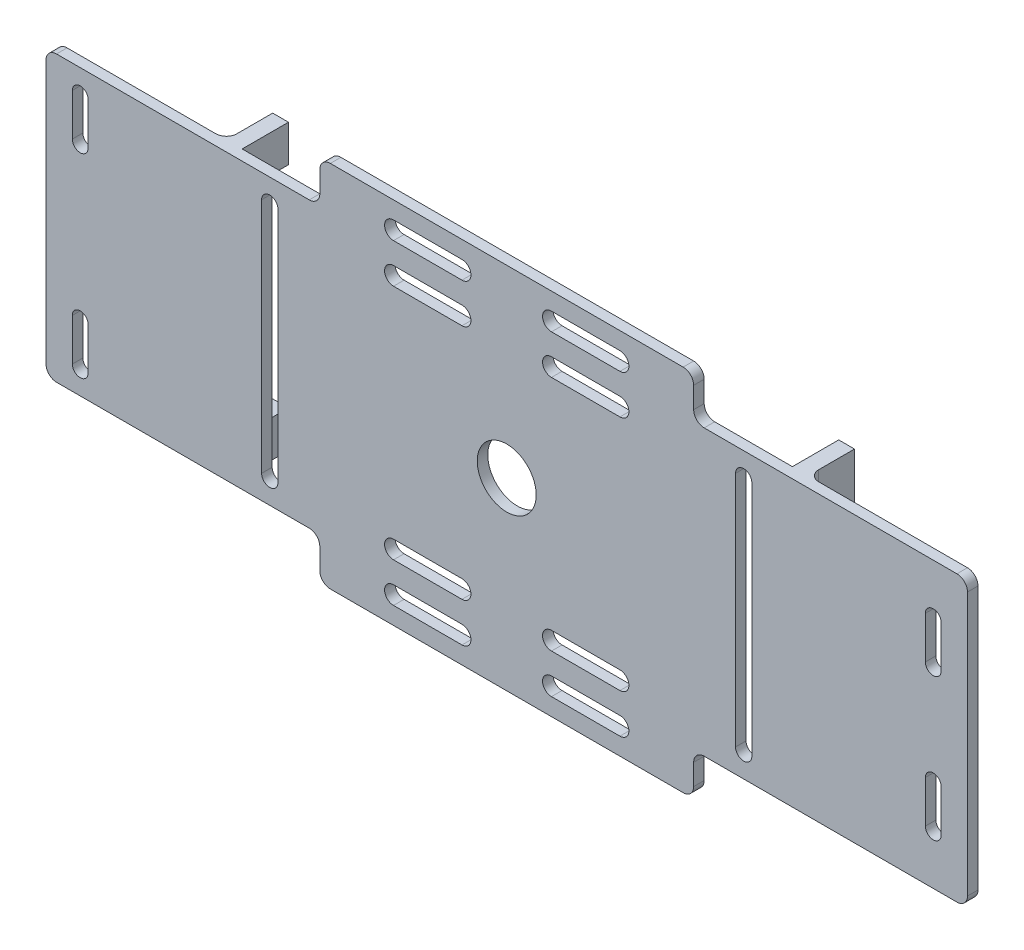
SolidWorks part; units mm, degrees
ref_plane "前基準面" through (0, 0, 0) normal (0, 0, 1) x (1, 0, 0)
ref_plane "上基準面" through (0, 0, 0) normal (0, 1, 0) x (1, 0, 0)
ref_plane "右基準面" through (0, 0, 0) normal (1, 0, 0) x (0, 0, -1)
sketch "草圖1" plane through (0, 0, 0) normal (0, 0, 1) x (1, 0, 0)
  line L0 (35.5, 33) -> (35.5, 29)
  line L1 (-33.5, 35) -> (33.5, 35)
  line L2 (-87.5, 25) -> (-87.5, -25)
  line L3 (-33.5, -35) -> (33.5, -35)
  line L4 (87.5, 25) -> (87.5, -25)
  line L5 (-85, 35) -> (85, -35) construction
  line L6 (-85, -35) -> (85, 35) construction
  line L7 (37.5, 27) -> (85.5, 27)
  line L8 (0, 72.342) -> (0, -45.5052) construction
  line L9 (-37.5, 27) -> (-85.5, 27)
  line L10 (124.9211, 0) -> (-91.026, 0) construction
  line L11 (-35.5, 33) -> (-35.5, 29)
  line L12 (37.5, -27) -> (85.5, -27)
  line L13 (35.5, -33) -> (35.5, -29)
  line L14 (-35.5, -33) -> (-35.5, -29)
  line L15 (-37.5, -27) -> (-85.5, -27)
  arc A0 (35.5, 33) -> (33.5, 35) centre (33.5, 33) ccw
  arc A1 (37.5, 27) -> (35.5, 29) centre (37.5, 29) cw
  arc A2 (87.5, 25) -> (85.5, 27) centre (85.5, 25) ccw
  arc A3 (-87.5, 25) -> (-85.5, 27) centre (-85.5, 25) cw
  arc A4 (-37.5, 27) -> (-35.5, 29) centre (-37.5, 29) ccw
  arc A5 (-35.5, 33) -> (-33.5, 35) centre (-33.5, 33) cw
  arc A6 (87.5, -25) -> (85.5, -27) centre (85.5, -25) cw
  arc A7 (37.5, -27) -> (35.5, -29) centre (37.5, -29) ccw
  arc A8 (35.5, -33) -> (33.5, -35) centre (33.5, -33) cw
  arc A9 (-35.5, -33) -> (-33.5, -35) centre (-33.5, -33) ccw
  arc A10 (-37.5, -27) -> (-35.5, -29) centre (-37.5, -29) cw
  arc A11 (-87.5, -25) -> (-85.5, -27) centre (-85.5, -25) ccw
  point P0 (0, 0)
  point P13 (35.5, 27)
  point P29 (-35.5, 27)
  point P39 (35.5, -27)
  point P49 (-35.5, -27)
  dimension "D1" = 2
  dimension "D2" = 2
  dimension "D3" = 2
  dimension "D4" = 175
  dimension "D5" = 70
  dimension "D6" = 52
  dimension "D7" = 8
extrude "填料-伸長1" add sketch "草圖1" along normal blind 2
sketch "草圖2" plane through (0, 0, 2) normal (0, 0, 1) x (1, 0, 0)
  line L0 (-1000, 0) -> (49000, 0) construction
  line L1 (45, -986.1952) -> (45, 49013.8048) construction
  line L2 (-81, -962.7943) -> (-81, 49037.2057) construction
  line L3 (45, -22.5) -> (45, 22.5) construction
  line L4 (43.45, -22.5) -> (43.45, 22.5)
  line L5 (46.55, -22.5) -> (46.55, 22.5)
  line L6 (-45, -1000) -> (-45, 49000) construction
  line L7 (-45, -22.5) -> (-45, 22.5) construction
  line L8 (-46.55, -22.5) -> (-46.55, 22.5)
  line L9 (-43.45, -22.5) -> (-43.45, 22.5)
  line L10 (0, -1000) -> (0, 49000) construction
  line L11 (-1005.6924, 30) -> (48994.3076, 30) construction
  line L12 (-1002.3566, -30) -> (48997.6434, -30) construction
  line L13 (21.5, 30) -> (8.5, 30) construction
  line L16 (21.5, 28.3) -> (8.5, 28.3)
  line L19 (81, -968.4295) -> (81, 49031.5705) construction
  line L20 (-81, -22.5) -> (-81, 22.5) construction
  line L21 (-82.5, -22.5) -> (-82.5, 22.5) construction
  line L22 (-79.5, -22.5) -> (-79.5, 22.5) construction
  line L23 (81, -17.5) -> (81, 17.5) construction
  line L24 (79.5, -17.5) -> (79.5, 17.5) construction
  line L25 (82.5, -17.5) -> (82.5, 17.5) construction
  line L26 (21.5, 31.7) -> (8.5, 31.7)
  line L27 (21.5, 22.5) -> (8.5, 22.5) construction
  line L28 (21.5, 20.8) -> (8.5, 20.8)
  line L29 (21.5, 24.2) -> (8.5, 24.2)
  line L30 (-21.5, 30) -> (-8.5, 30) construction
  line L31 (-21.5, 28.3) -> (-8.5, 28.3)
  line L32 (-21.5, 31.7) -> (-8.5, 31.7)
  line L33 (-21.5, 22.5) -> (-8.5, 22.5) construction
  line L34 (-21.5, 20.8) -> (-8.5, 20.8)
  line L35 (-21.5, 24.2) -> (-8.5, 24.2)
  line L36 (21.5, -30) -> (8.5, -30) construction
  line L37 (21.5, -28.3) -> (8.5, -28.3)
  line L38 (21.5, -31.7) -> (8.5, -31.7)
  line L39 (21.5, -22.5) -> (8.5, -22.5) construction
  line L40 (21.5, -20.8) -> (8.5, -20.8)
  line L41 (21.5, -24.2) -> (8.5, -24.2)
  line L42 (-21.5, -30) -> (-8.5, -30) construction
  line L43 (-21.5, -28.3) -> (-8.5, -28.3)
  line L44 (-21.5, -31.7) -> (-8.5, -31.7)
  line L45 (-21.5, -22.5) -> (-8.5, -22.5) construction
  line L46 (-21.5, -20.8) -> (-8.5, -20.8)
  line L47 (-21.5, -24.2) -> (-8.5, -24.2)
  line L48 (79.5, 9.5) -> (79.5, 17.5)
  line L49 (82.5, 17.5) -> (82.5, 9.5)
  line L50 (82.5, -17.5) -> (82.5, -9.5)
  line L51 (79.5, -9.5) -> (79.5, -17.5)
  line L52 (-82.5, 22.5) -> (-82.5, 14.5)
  line L53 (-79.5, 22.5) -> (-79.5, 14.5)
  line L54 (-79.5, -22.5) -> (-79.5, -14.5)
  line L55 (-82.5, -22.5) -> (-82.5, -14.5)
  arc A0 (43.45, -22.5) -> (46.55, -22.5) centre (45, -22.5) ccw
  arc A1 (46.55, 22.5) -> (43.45, 22.5) centre (45, 22.5) ccw
  arc A2 (-46.55, -22.5) -> (-43.45, -22.5) centre (-45, -22.5) ccw
  arc A3 (-43.45, 22.5) -> (-46.55, 22.5) centre (-45, 22.5) ccw
  arc A12 (-82.5, -22.5) -> (-79.5, -22.5) centre (-81, -22.5) ccw construction
  arc A13 (-79.5, 22.5) -> (-82.5, 22.5) centre (-81, 22.5) ccw construction
  arc A14 (79.5, -17.5) -> (82.5, -17.5) centre (81, -17.5) ccw construction
  arc A15 (82.5, 17.5) -> (79.5, 17.5) centre (81, 17.5) ccw construction
  circle A16 centre (0, 0) radius 5.6
  arc A17 (21.5, 28.3) -> (21.5, 31.7) centre (21.5, 30) ccw
  arc A18 (8.5, 31.7) -> (8.5, 28.3) centre (8.5, 30) ccw
  arc A19 (21.5, 20.8) -> (21.5, 24.2) centre (21.5, 22.5) ccw
  arc A20 (8.5, 24.2) -> (8.5, 20.8) centre (8.5, 22.5) ccw
  arc A21 (-21.5, 28.3) -> (-21.5, 31.7) centre (-21.5, 30) cw
  arc A22 (-8.5, 31.7) -> (-8.5, 28.3) centre (-8.5, 30) cw
  arc A23 (-21.5, 20.8) -> (-21.5, 24.2) centre (-21.5, 22.5) cw
  arc A24 (-8.5, 24.2) -> (-8.5, 20.8) centre (-8.5, 22.5) cw
  arc A25 (21.5, -28.3) -> (21.5, -31.7) centre (21.5, -30) cw
  arc A26 (8.5, -31.7) -> (8.5, -28.3) centre (8.5, -30) cw
  arc A27 (21.5, -20.8) -> (21.5, -24.2) centre (21.5, -22.5) cw
  arc A28 (8.5, -24.2) -> (8.5, -20.8) centre (8.5, -22.5) cw
  arc A29 (-21.5, -28.3) -> (-21.5, -31.7) centre (-21.5, -30) ccw
  arc A30 (-8.5, -31.7) -> (-8.5, -28.3) centre (-8.5, -30) ccw
  arc A31 (-21.5, -20.8) -> (-21.5, -24.2) centre (-21.5, -22.5) ccw
  arc A32 (-8.5, -24.2) -> (-8.5, -20.8) centre (-8.5, -22.5) ccw
  arc A33 (82.5, 9.5) -> (79.5, 9.5) centre (81, 9.5) cw
  arc A34 (82.5, -9.5) -> (79.5, -9.5) centre (81, -9.5) ccw
  arc A35 (79.5, 17.5) -> (82.5, 17.5) centre (81, 17.5) cw
  arc A36 (79.5, -17.5) -> (82.5, -17.5) centre (81, -17.5) ccw
  arc A37 (-82.5, -22.5) -> (-79.5, -22.5) centre (-81, -22.5) ccw
  arc A38 (-82.5, 22.5) -> (-79.5, 22.5) centre (-81, 22.5) cw
  arc A39 (-82.5, 14.5) -> (-79.5, 14.5) centre (-81, 14.5) ccw
  arc A40 (-82.5, -14.5) -> (-79.5, -14.5) centre (-81, -14.5) cw
  point P9 (45, 0)
  point P16 (-45, 0)
  point P31 (15, 30)
  point P39 (15, 22.5)
  point P47 (-81, 0)
  point P54 (81, 0)
  point P63 (-15, 30)
  point P70 (-15, 22.5)
  point P77 (15, -30)
  point P84 (15, -22.5)
  point P91 (-15, -30)
  point P98 (-15, -22.5)
  dimension "D10" = 1.7
  dimension "D20" = 11.2
  dimension "D12" = 8.5
  dimension "D22" = 8
  dimension "D23" = 8
  dimension "D2" = 45
  dimension "D3" = 3.1
  dimension "D4" = 90
  dimension "D5" = 45
  dimension "D6" = 3.1
  dimension "D7" = 45
  dimension "D8" = 60
  dimension "D9" = 30
  dimension "D11" = 13
  dimension "D13" = 2
  dimension "D14" = 162
  dimension "D15" = 81
  dimension "D16" = 3
  dimension "D17" = 45
  dimension "D18" = 35
  dimension "D19" = 3
  dimension "D21" = 7.5
extrude "除料-伸長1" cut sketch "草圖2" against normal through all
sketch "草圖5" plane through (0, 0, 2) normal (0, 0, 1) x (1, 0, 0)
  line L1 (-55.25, 27) -> (-52.25, 27)
  line L2 (-55.25, 27) -> (-55.25, -27)
  line L3 (-55.25, -27) -> (-52.25, -27)
  line L4 (-52.25, 27) -> (-52.25, -27)
  line L6 (0, 48.2539) -> (0, -45.9001) construction
  line L7 (52.25, 27) -> (52.25, -27)
  line L8 (55.25, -27) -> (52.25, -27)
  line L9 (55.25, 27) -> (55.25, -27)
  line L10 (55.25, 27) -> (52.25, 27)
  line L11 (-37.5, 27) -> (-85.5, 27) construction
  line L13 (-85.5, -27) -> (-37.5, -27) construction
  dimension "D1" = 3
  dimension "D2" = 52.25
extrude "填料-伸長2" add sketch "草圖5" against normal blind 10.8 contours L2 L3 L4 L1 | L7 L8 L9 L10
fillet "圓角1" radius 2 1 edges at (55.25, 0, 0)
sketch "草圖6" plane through (0, 0, -8.8) normal (0, 0, -1) x (-1, 0, 0)
  line L0 (-19.1896, 0) -> (94.9262, 0) construction
  line L1 (55.25, 27) -> (55.25, -27) construction
  line L2 (52.25, -20) -> (55.25, -20)
  line L3 (52.25, -20) -> (52.25, 20)
  line L4 (52.25, 20) -> (55.25, 20)
  line L5 (55.25, -20) -> (55.25, 20)
  line L6 (52.25, -20) -> (55.25, 20) construction
  line L7 (52.25, 20) -> (55.25, -20) construction
  line L8 (52.25, 27) -> (52.25, -27) construction
  point P2 (53.75, 0)
  dimension "D1" = 40
extrude "除料-伸長3" cut sketch "草圖6" against normal blind 6
fillet "圓角2" radius 2 2 edges at (-53.75, -20, -2.8) (-53.75, 20, -2.8)
fillet "圓角3" radius 2 1 edges at (-55.25, 0, 0)
